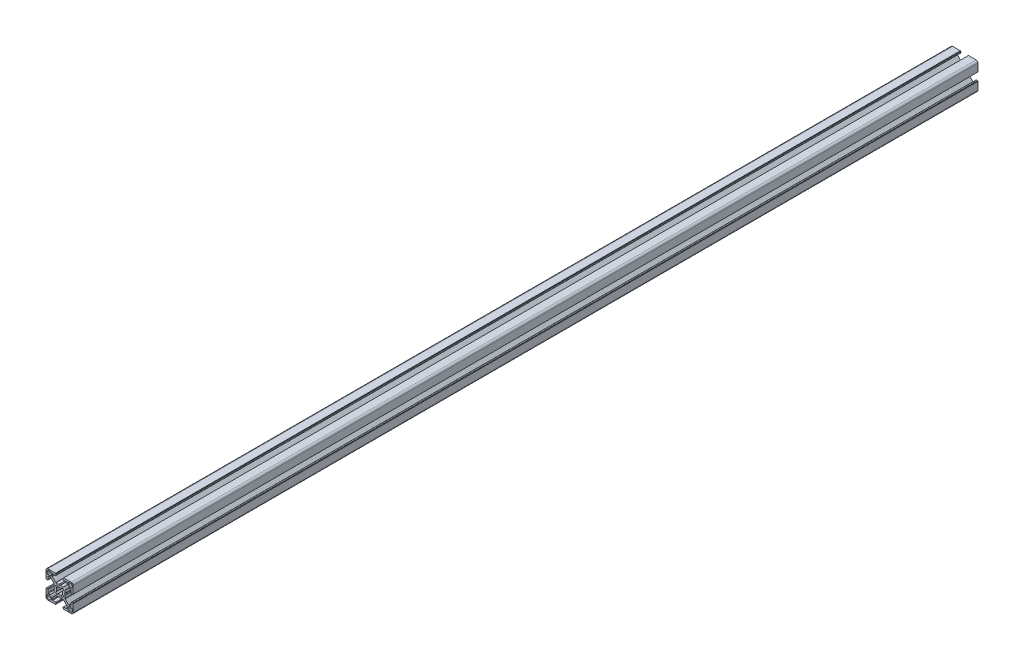
SolidWorks part; units mm, degrees
ref_plane "Front Plane" through (0, 0, 0) normal (0, 0, 1) x (1, 0, 0)
ref_plane "Top Plane" through (0, 0, 0) normal (0, 1, 0) x (1, 0, 0)
ref_plane "Right Plane" through (0, 0, 0) normal (1, 0, 0) x (0, 0, -1)
sketch "Sketch1" plane through (0, 0, 0) normal (0, 0, 1) x (1, 0, 0)
  line L0 (-15, 0) -> (15, 0) construction
  line L1 (0, -15) -> (0, 15) construction
  line L2 (-4.5, 15) -> (4.5, 15) construction
  line L3 (-4, -15) -> (4, -15) construction
  line L4 (-4.5, 15) -> (-4.5, 14.5)
  line L5 (-4.5, 14.5) -> (-4, 14.5)
  line L6 (-4, 14.5) -> (-4, 13.29)
  line L7 (-4.5, 12.79) -> (-7.7675, 12.79)
  line L8 (-8.2675, 12.29) -> (-8.2675, 10.2707)
  line L9 (-8.1211, 9.9171) -> (-4.3504, 6.1464)
  line L10 (-3.9968, 6) -> (0, 6)
  line L11 (0, 0) -> (-15, 15) construction
  line L12 (-4.5, 15) -> (-12.968, 15)
  line L14 (-12.705, 9.5135) -> (-10.5135, 9.5135)
  line L15 (-13.705, 10.5135) -> (-13.705, 12.705)
  line L16 (-12.705, 13.705) -> (-10.5135, 13.705)
  line L17 (-9.5135, 10.5135) -> (-9.5135, 12.705)
  line L18 (-13.705, 9.5135) -> (-9.5135, 13.705) construction
  line L19 (-13.705, 13.705) -> (-9.5135, 9.5135) construction
  line L20 (-3.1568, 4.5038) -> (-1.5303, 3.1477) construction
  line L21 (-4.5038, 3.1568) -> (-3.1477, 1.5303) construction
  line L22 (-6, 3.9968) -> (-6, 0)
  line L23 (-9.9171, 8.1211) -> (-6.1464, 4.3504)
  line L24 (-15, 4.5) -> (-15, 12.968)
  line L25 (-12.29, 8.2675) -> (-10.2707, 8.2675)
  line L26 (-12.79, 4.5) -> (-12.79, 7.7675)
  line L27 (-14.5, 4) -> (-13.29, 4)
  line L28 (-14.5, 4.5) -> (-14.5, 4)
  line L29 (-15, 4.5) -> (-14.5, 4.5)
  circle A0 centre (0, 0) radius 3.5
  arc A1 (-12.968, 15) -> (-15, 12.968) centre (-12.968, 12.968) ccw
  circle A2 centre (0, 0) radius 5.5 construction
  arc A3 (-10.5135, 9.5135) -> (-9.5135, 10.5135) centre (-10.5135, 10.5135) ccw
  arc A4 (-13.705, 12.705) -> (-12.705, 13.705) centre (-12.705, 12.705) cw
  arc A5 (-10.5135, 13.705) -> (-9.5135, 12.705) centre (-10.5135, 12.705) cw
  arc A6 (-12.705, 9.5135) -> (-13.705, 10.5135) centre (-12.705, 10.5135) cw
  arc A7 (-12.79, 4.5) -> (-13.29, 4) centre (-13.29, 4.5) cw
  arc A8 (-12.29, 8.2675) -> (-12.79, 7.7675) centre (-12.29, 7.7675) ccw
  arc A9 (-9.9171, 8.1211) -> (-10.2707, 8.2675) centre (-10.2707, 7.7675) ccw
  arc A10 (-6, 3.9968) -> (-6.1464, 4.3504) centre (-6.5, 3.9968) ccw
  arc A11 (-4.3504, 6.1464) -> (-3.9968, 6) centre (-3.9968, 6.5) ccw
  arc A12 (-4, 13.29) -> (-4.5, 12.79) centre (-4.5, 13.29) cw
  arc A13 (-7.7675, 12.79) -> (-8.2675, 12.29) centre (-7.7675, 12.29) ccw
  arc A14 (-8.2675, 10.2707) -> (-8.1211, 9.9171) centre (-7.7675, 10.2707) ccw
  point P4 (0, 0)
  point P8 (0, 0)
  point P13 (0, 15)
  point P15 (0, -15)
  point P16 (0, 6)
  point P23 (-11.6092, 11.6093)
  point P26 (0, 6)
  point P62 (-12.79, 4)
  point P65 (-12.79, 8.2675)
  point P68 (-10.0636, 8.2675)
  point P71 (-6, 4.2039)
  point P74 (-4.2039, 6)
  point P77 (-4, 12.79)
  point P80 (-8.2675, 12.79)
  point P83 (-8.2675, 10.0636)
  dimension "Center Hole Diameter" = 7
  dimension "D11" = 2.032
  dimension "D9" = 11
  dimension "D13" = 1
  dimension "D14" = 0.5
  dimension "Rail Height" = 30
  dimension "Rail Width" = 30
  dimension "T-Slot Width" = 8
  dimension "T-Slot Depth" = 9
  dimension "D1" = 9
  dimension "D2" = 45
  dimension "D3" = 8
  dimension "D4" = 2.21
  dimension "D5" = 16.535
  dimension "D7" = 2.54
  dimension "D6" = 1.295
  dimension "D8" = 1.246
  dimension "D10" = 10.36
  dimension "D12" = 1.905
sketch "Sketch2" plane through (0, 0, 0) normal (1, 0, 0) x (0, 0, -1)
  line L0 (-76.2, 0) -> (76.2, 0) construction
  line L2 (0, -15) -> (0, 15) construction
  line L3 (0, -15) -> (0, 15) construction
  line L4 (-76.2, -15) -> (-76.2, 15) construction
  line L5 (76.2, -15) -> (76.2, 15) construction
  point P0 (-38.7, 0)
  point P3 (0, 0)
  point P4 (38.7, 0)
  point P12 (-76.2, 0)
  point P14 (76.2, 0)
  dimension "Length" = 152.4
  dimension "D1" = 37.5
sketch "Sketch3" plane through (0, 0, 0) normal (0, 0, 1) x (1, 0, 0)
  line L0 (-4.5038, 3.1568) -> (-3.1477, 1.5303)
  line L1 (0, 3.5) -> (0, 5.5)
  line L2 (-5.5, 0) -> (-3.5, 0)
  line L7 (-6, 3.9968) -> (-6, 0) construction
  line L31 (-9.9171, 8.1211) -> (-6.1464, 4.3504) construction
  line L117 (-12.29, 8.2675) -> (-10.2707, 8.2675) construction
  line L118 (-12.79, 4.5) -> (-12.79, 7.7675) construction
  line L157 (-12.705, 9.5135) -> (-10.5135, 9.5135)
  line L158 (-9.5135, 10.5135) -> (-9.5135, 12.705)
  line L163 (-10.5135, 13.705) -> (-12.705, 13.705)
  line L164 (-13.705, 12.705) -> (-13.705, 10.5135)
  line L165 (-12.705, 9.5135) -> (-10.5135, 9.5135)
  line L166 (-9.5135, 10.5135) -> (-9.5135, 12.705)
  line L167 (-10.5135, 13.705) -> (-12.705, 13.705)
  line L168 (-13.705, 12.705) -> (-13.705, 10.5135)
  line L169 (-14.5, 4) -> (-13.29, 4) construction
  line L170 (-14.5, 4.5) -> (-14.5, 4) construction
  line L171 (-15, 4.5) -> (-14.5, 4.5) construction
  line L172 (-15, 4.5) -> (-15, 12.968) construction
  line L173 (-4.5, 15) -> (-12.968, 15) construction
  line L174 (-4.5, 15) -> (-4.5, 14.5) construction
  line L175 (-4.5, 14.5) -> (-4, 14.5) construction
  line L176 (-4, 14.5) -> (-4, 13.29) construction
  line L177 (-4.5, 12.79) -> (-7.7675, 12.79) construction
  line L178 (-8.2675, 12.29) -> (-8.2675, 10.2707) construction
  line L179 (-8.1211, 9.9171) -> (-4.3504, 6.1464) construction
  line L180 (-3.9968, 6) -> (0, 6) construction
  line L181 (-6, 3.9968) -> (-6, 0.866)
  line L182 (-9.9171, 8.1211) -> (-6.1464, 4.3504)
  line L183 (-12.29, 8.2675) -> (-10.2707, 8.2675)
  line L184 (-12.79, 4.5) -> (-12.79, 7.7675)
  line L185 (-14.5, 4) -> (-13.29, 4)
  line L186 (-14.5, 4.5) -> (-14.5, 4)
  line L187 (-15, 4.5) -> (-14.5, 4.5)
  line L188 (-15, 4.5) -> (-15, 12.968)
  line L189 (-4.5, 15) -> (-12.968, 15)
  line L190 (-4.5, 15) -> (-4.5, 14.5)
  line L191 (-4.5, 14.5) -> (-4, 14.5)
  line L192 (-4, 14.5) -> (-4, 13.29)
  line L193 (-4.5, 12.79) -> (-7.7675, 12.79)
  line L194 (-8.2675, 12.29) -> (-8.2675, 10.2707)
  line L195 (-8.1211, 9.9171) -> (-4.3504, 6.1464)
  line L196 (-3.9968, 6) -> (-0.866, 6)
  line L197 (-0.866, 6) -> (0, 5.5)
  line L198 (0, -15) -> (0, 15) construction
  line L199 (0, 0) -> (-15, 15) construction
  line L200 (0, 0) -> (-15, 15) construction
  line L201 (-3.1568, 4.5038) -> (-1.5303, 3.1477) construction
  line L202 (-3.1568, 4.5038) -> (-1.5303, 3.1477)
  line L203 (-6, 0.866) -> (-5.5, 0)
  line L204 (-15, 0) -> (15, 0) construction
  line L205 (-15, 0) -> (15, 0) construction
  line L206 (0, -15) -> (0, 15) construction
  arc A0 (-3.5, 0) -> (-3.1477, 1.5303) centre (0, 0) cw
  arc A10 (-6, 3.9968) -> (-6.1464, 4.3504) centre (-6.5, 3.9968) ccw construction
  circle A16 centre (0, 0) radius 3.5
  arc A18 (0, 3.5) -> (-1.5303, 3.1477) centre (0, 0) ccw
  arc A20 (-9.9171, 8.1211) -> (-10.2707, 8.2675) centre (-10.2707, 7.7675) ccw construction
  arc A22 (-12.29, 8.2675) -> (-12.79, 7.7675) centre (-12.29, 7.7675) ccw construction
  arc A28 (-13.29, 4) -> (-12.79, 4.5) centre (-13.29, 4.5) ccw construction
  arc A29 (-10.5135, 9.5135) -> (-9.5135, 10.5135) centre (-10.5135, 10.5135) ccw
  arc A30 (-9.5135, 12.705) -> (-10.5135, 13.705) centre (-10.5135, 12.705) ccw
  arc A31 (-12.705, 13.705) -> (-13.705, 12.705) centre (-12.705, 12.705) ccw
  arc A32 (-13.705, 10.5135) -> (-12.705, 9.5135) centre (-12.705, 10.5135) ccw
  arc A33 (-10.5135, 9.5135) -> (-9.5135, 10.5135) centre (-10.5135, 10.5135) ccw
  arc A34 (-9.5135, 12.705) -> (-10.5135, 13.705) centre (-10.5135, 12.705) ccw
  arc A35 (-12.705, 13.705) -> (-13.705, 12.705) centre (-12.705, 12.705) ccw
  arc A36 (-13.705, 10.5135) -> (-12.705, 9.5135) centre (-12.705, 10.5135) ccw
  arc A37 (-12.968, 15) -> (-15, 12.968) centre (-12.968, 12.968) ccw construction
  arc A38 (-4.5, 12.79) -> (-4, 13.29) centre (-4.5, 13.29) ccw construction
  arc A39 (-7.7675, 12.79) -> (-8.2675, 12.29) centre (-7.7675, 12.29) ccw construction
  arc A40 (-8.2675, 10.2707) -> (-8.1211, 9.9171) centre (-7.7675, 10.2707) ccw construction
  arc A41 (-4.3504, 6.1464) -> (-3.9968, 6) centre (-3.9968, 6.5) ccw construction
  arc A42 (-6, 3.9968) -> (-6.1464, 4.3504) centre (-6.5, 3.9968) ccw
  arc A43 (-9.9171, 8.1211) -> (-10.2707, 8.2675) centre (-10.2707, 7.7675) ccw
  arc A44 (-12.29, 8.2675) -> (-12.79, 7.7675) centre (-12.29, 7.7675) ccw
  arc A45 (-13.29, 4) -> (-12.79, 4.5) centre (-13.29, 4.5) ccw
  arc A46 (-12.968, 15) -> (-15, 12.968) centre (-12.968, 12.968) ccw
  arc A47 (-4.5, 12.79) -> (-4, 13.29) centre (-4.5, 13.29) ccw
  arc A48 (-7.7675, 12.79) -> (-8.2675, 12.29) centre (-7.7675, 12.29) ccw
  arc A49 (-8.2675, 10.2707) -> (-8.1211, 9.9171) centre (-7.7675, 10.2707) ccw
  arc A50 (-4.3504, 6.1464) -> (-3.9968, 6) centre (-3.9968, 6.5) ccw
  circle A51 centre (0, 0) radius 5.5 construction
  arc A52 (-3.1568, 4.5038) -> (-4.5038, 3.1568) centre (0, 0) ccw
  dimension "D3" = 60
  dimension "D4" = 60
  dimension "D1" = 0
  dimension "D2" = 0
extrude "Boss-Extrude1" add sketch "Sketch3" along normal mid plane 1000
pattern_circular "CirPattern1" count 4 over 360 about axis through (0, 0, 76.2) along (0, 0, -1) of "Boss-Extrude1"
ref_plane "Contact Plane1" through (15, 0, 0) normal (1, 0, 0) x (0, 0, -1)
ref_plane "Contact Plane2" through (0, -15, 0) normal (0, 1, 0) x (1, 0, 0)
ref_plane "Contact Plane3" through (-15, 0, 0) normal (1, 0, 0) x (0, 0, -1)
ref_plane "Contact Plane4" through (0, 15, 0) normal (0, 1, 0) x (1, 0, 0)
equation "\"D1@Sketch2\" = \"Rail Height@Sketch1\" * 1.25"
equation "\"D1@Sketch1\"=\"T-Slot Width@Sketch1\"+1mm"
equation "\"D3@Sketch1\"=\"T-Slot Width@Sketch1\""
equation "\"D1@Boss-Extrude1\"=\"length\""
equation "\"length\"= 1000"
